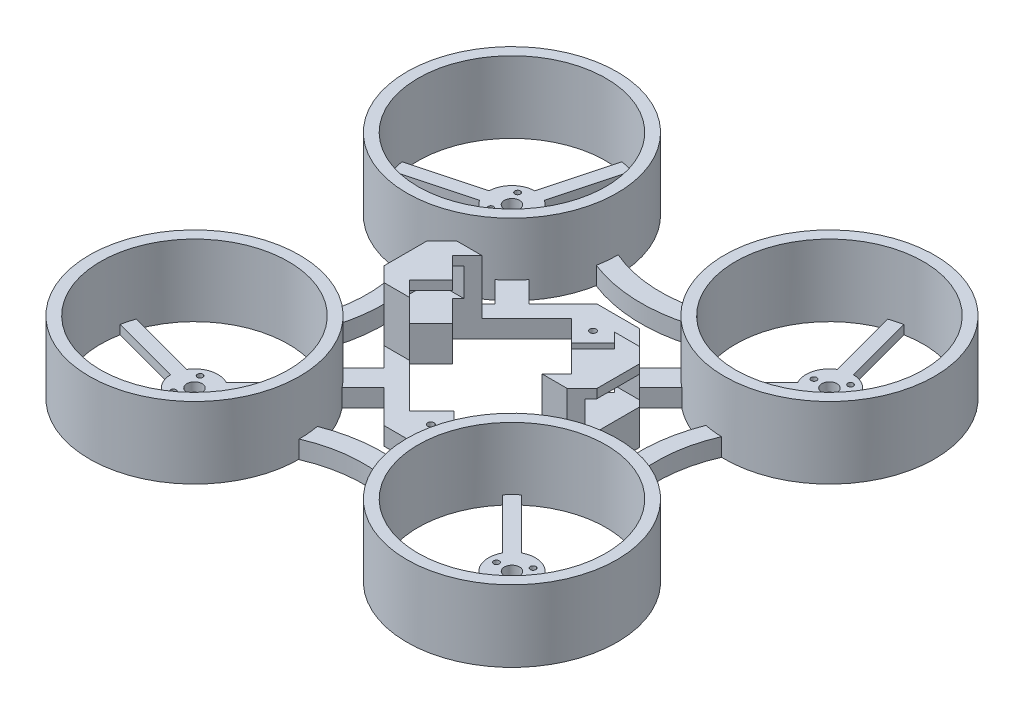
SolidWorks part; units mm, degrees
ref_plane "Front Plane" through (0, 0, 0) normal (0, 0, 1) x (1, 0, 0)
ref_plane "Top Plane" through (0, 0, 0) normal (0, 1, 0) x (1, 0, 0)
ref_plane "Right Plane" through (0, 0, 0) normal (1, 0, 0) x (0, 0, -1)
sketch "Sketch2" plane through (0, 0, 0) normal (0, 1, 0) x (1, 0, 0)
  line L0 (-4.78, 18.125) -> (0, 13.345)
  line L6 (0, 13.345) -> (4.78, 18.125)
  line L11 (-18.1231, 4.7819) -> (-13.3431, 0.0019)
  line L12 (-13.3431, 0.0019) -> (-18.1231, -4.7782)
  line L13 (18.1231, 4.7819) -> (13.3431, 0.0019)
  line L14 (13.3431, 0.0019) -> (18.1231, -4.7782)
  line L15 (4.78, 18.125) -> (18.1231, 4.7819)
  line L17 (4.9922, -17.9092) -> (0, -12.917)
  line L18 (0, -12.917) -> (-4.9922, -17.9092)
  line L23 (18.1231, -4.7782) -> (4.9922, -17.9092)
  line L24 (-4.9922, -17.9092) -> (-18.1231, -4.7782)
  line L25 (-18.1231, 4.7819) -> (-4.78, 18.125)
  line L27 (-55, 0) -> (55, 0) construction
  line L33 (0, -55) -> (0, 55) construction
  line L40 (31.5229, -56.1137) -> (35.6423, -40.74)
  line L41 (28.6252, -55.3372) -> (32.7445, -39.9635)
  line L42 (55.3398, -28.6226) -> (39.9661, -32.742)
  line L43 (55.3398, 28.6226) -> (39.9661, 32.742)
  line L44 (28.6252, 55.3372) -> (32.7445, 39.9635)
  line L45 (56.1162, 31.5204) -> (40.7425, 35.6397)
  line L46 (31.5229, 56.1137) -> (35.6423, 40.74)
  line L47 (56.1162, -31.5204) -> (40.7425, -35.6397)
  line L48 (-28.6252, -55.3372) -> (-32.7445, -39.9635)
  line L49 (-31.5229, -56.1137) -> (-35.6423, -40.74)
  line L50 (-56.1162, -31.5204) -> (-40.7425, -35.6397)
  line L51 (-55.3398, -28.6226) -> (-39.9661, -32.742)
  line L52 (-31.5229, 56.1137) -> (-35.6423, 40.74)
  line L53 (-28.6252, 55.3372) -> (-32.7445, 39.9635)
  line L54 (-55.3398, 28.6226) -> (-39.9661, 32.742)
  line L55 (-56.1162, 31.5204) -> (-40.7425, 35.6397)
  line L56 (-30.8775, 32.9969) -> (-19.6231, 21.7425)
  line L57 (-32.9965, 30.8765) -> (-21.7426, 19.6226)
  line L59 (23.7763, 4.7819) -> (23.7763, -4.7819)
  line L60 (-16.1636, 12.3946) -> (-20.8687, 17.0996)
  line L61 (30.8775, 32.9969) -> (19.6231, 21.7425)
  line L62 (32.9965, 30.8765) -> (21.7426, 19.6226)
  line L63 (-12.3927, 16.1655) -> (-17.0982, 20.871)
  line L65 (12.3927, 16.1655) -> (17.0982, 20.871)
  line L66 (16.1636, 12.3946) -> (20.8687, 17.0996)
  line L70 (32.9965, -30.8765) -> (21.7426, -19.6226)
  line L71 (30.8775, -32.9969) -> (19.6231, -21.7425)
  line L72 (-30.8775, -32.9969) -> (-19.6231, -21.7425)
  line L73 (-32.9965, -30.8765) -> (-21.7426, -19.6226)
  line L75 (-12.3927, -16.1655) -> (-17.0982, -20.871)
  line L76 (-16.1636, -12.3946) -> (-20.8687, -17.0996)
  line L85 (4.9922, -23.566) -> (12.3927, -16.1655)
  line L86 (12.3927, -16.1655) -> (17.0982, -20.871)
  line L87 (16.1636, -12.3946) -> (20.8687, -17.0996)
  line L90 (-23.7763, 4.7819) -> (-23.7763, -4.7819)
  line L91 (-23.7763, 4.7819) -> (-16.1636, 12.3946)
  line L92 (4.78, 23.7781) -> (12.3927, 16.1655)
  line L93 (23.7763, 4.7819) -> (16.1636, 12.3946)
  line L94 (-4.9922, -23.566) -> (4.9922, -23.566)
  line L96 (4.78, 23.7781) -> (-4.78, 23.7781)
  line L97 (-4.78, 23.7781) -> (-12.3927, 16.1655)
  line L98 (16.1636, -12.3946) -> (23.7763, -4.7819)
  line L99 (-4.9922, -23.566) -> (-12.3927, -16.1655)
  line L100 (-16.1636, -12.3946) -> (-23.7763, -4.7819)
  circle A0 centre (0, 18.125) radius 0.7
  circle A1 centre (18.1231, 0.0019) radius 0.7
  circle A2 centre (0, -18.1213) radius 0.7
  circle A3 centre (-18.1231, 0.0019) radius 0.7
  circle A4 centre (-35.4954, 35.4928) radius 5.2492
  circle A5 centre (-32.0291, 35.4951) radius 0.625
  circle A6 centre (-37.2253, 32.4951) radius 0.625
  circle A7 centre (-37.2253, 38.4951) radius 0.625
  circle A8 centre (-35.4954, 35.4928) radius 1.7
  arc A9 (-30.8775, 32.9969) -> (-32.9965, 30.8765) centre (-35.4954, 35.4928) cw
  circle A10 centre (-37.2253, -38.4951) radius 0.625
  circle A11 centre (-32.0291, -35.4951) radius 0.625
  circle A12 centre (-37.2253, -32.4951) radius 0.625
  circle A13 centre (-35.4954, -35.4928) radius 1.7
  circle A14 centre (-35.4954, -35.4928) radius 5.2492
  arc A15 (-30.8775, -32.9969) -> (-32.9965, -30.8765) centre (-35.4954, -35.4928) ccw
  circle A16 centre (37.2253, 38.4951) radius 0.625
  circle A17 centre (32.0291, 35.4951) radius 0.625
  circle A18 centre (35.4954, 35.4928) radius 1.7
  circle A19 centre (37.2253, 32.4951) radius 0.625
  circle A20 centre (35.4954, 35.4928) radius 5.2492
  circle A21 centre (37.2253, -38.4951) radius 0.625
  circle A22 centre (37.2253, -32.4951) radius 0.625
  circle A23 centre (32.0291, -35.4951) radius 0.625
  circle A24 centre (35.4954, -35.4928) radius 1.7
  circle A25 centre (35.4954, -35.4928) radius 5.2492
  arc A26 (30.8775, 32.9969) -> (32.9965, 30.8765) centre (35.4954, 35.4928) ccw
  arc A27 (30.8775, -32.9969) -> (32.9965, -30.8765) centre (35.4954, -35.4928) cw
  circle A28 centre (35.4954, -35.4928) radius 21
  circle A29 centre (-35.4954, -35.4928) radius 21
  circle A30 centre (35.4954, 35.4928) radius 21
  circle A31 centre (-35.4954, 35.4928) radius 21
  circle A32 centre (35.4954, -35.4928) radius 23.5
  circle A33 centre (-35.4954, -35.4928) radius 23.5
  circle A34 centre (-35.4954, 35.4928) radius 23.5
  circle A35 centre (35.4954, 35.4928) radius 23.5
  arc A36 (55.3398, 28.6226) -> (56.1162, 31.5204) centre (35.4954, 35.4928) ccw
  arc A37 (39.9661, 32.742) -> (40.7425, 35.6397) centre (35.4954, 35.4928) ccw
  arc A38 (32.7445, 39.9635) -> (35.6423, 40.74) centre (35.4954, 35.4928) cw
  arc A39 (28.6252, 55.3372) -> (31.5229, 56.1137) centre (35.4954, 35.4928) cw
  arc A40 (-20.8687, 17.0996) -> (-17.0982, 20.871) centre (-35.4954, 35.4928) ccw
  arc A41 (20.8687, 17.0996) -> (17.0982, 20.871) centre (35.4954, 35.4928) cw
  arc A43 (-20.8687, -17.0996) -> (-17.0982, -20.871) centre (-35.4954, -35.4928) cw
  arc A44 (20.8687, -17.0996) -> (17.0982, -20.871) centre (35.4954, -35.4928) ccw
  arc A45 (30.9176, -12.443) -> (30.9176, 12.443) centre (62.3369, 0) cw
  arc A46 (34.8421, -12.0019) -> (30.9176, -12.443) centre (35.4954, -35.4928) ccw
  arc A47 (34.8421, 12.0019) -> (34.8421, -12.0019) centre (62.3369, 0) ccw
  arc A48 (-30.9176, 12.443) -> (-34.8421, 12.0019) centre (-35.4954, 35.4928) cw
  arc A49 (-34.8421, -12.0019) -> (-30.9176, -12.443) centre (-35.4954, -35.4928) cw
  arc A50 (-34.8421, 12.0019) -> (-34.8421, -12.0019) centre (-62.3369, 0) cw
  arc A51 (-30.9176, -12.443) -> (-30.9176, 12.443) centre (-62.3369, 0) ccw
  arc A52 (11.9679, 35.6936) -> (-11.9275, 35.676) centre (0, 63.203) cw
  arc A53 (11.9679, 35.6936) -> (12.3621, 31.1996) centre (35.4954, 35.4928) ccw
  arc A54 (12.3621, 31.1996) -> (-12.3239, 31.1847) centre (0, 62.8445) cw
  arc A55 (-11.9275, 35.676) -> (-12.3239, 31.1847) centre (-35.4954, 35.4928) cw
  arc A56 (30.9176, 12.443) -> (34.8421, 12.0019) centre (35.4954, 35.4928) ccw
  arc A57 (-11.9275, -35.676) -> (-12.3239, -31.1847) centre (-35.4954, -35.4928) ccw
  arc A58 (11.9679, -35.6936) -> (12.3621, -31.1996) centre (35.4954, -35.4928) cw
  arc A59 (12.3621, -31.1996) -> (-12.3239, -31.1847) centre (0, -62.8445) ccw
  arc A60 (11.9679, -35.6936) -> (-11.9275, -35.676) centre (0, -63.203) ccw
  point P162 (-34.8282, -11.5041)
  point P163 (-34.8282, -11.5021)
  point P164 (-30.7361, 11.9711)
  point P165 (-30.7364, 11.9694)
  dimension "D1" = 3.4
  dimension "D2" = 42
  dimension "D3" = 42
  dimension "D4" = 47
  dimension "D5" = 42
  dimension "D6" = 47
  dimension "D7" = 47
  dimension "D8" = 47
  dimension "D9" = 1.4
  dimension "D11" = 1.4
ref_plane "Plane2" through (0, 13, 0) normal (0, 1, 0) x (1, 0, 0)
extrude "Boss-Extrude4" add sketch "Sketch2<15>" along normal blind 2 separate body contours L72 A29 L73 A14 | L51 A29 L50 A14 | L49 A29 L48 A14 | A14 A12 A10 A11 A13 | L41 A28 L40 A25 | L70 A28 L71 A25 | A25 A21 A22 A23 A24 | L47 A28 L42 A25 | L57 A31 L56 A4 | L55 A31 L54 A4 | A4 A8 A7 A6 A5 | L53 A31 L52 A4 | L61 A30 L62 A20 | A20 A18 A16 A17 A19 | L46 A30 L44 A20 | L43 A30 L45 A20 region at (32.1102, 0, 48.1265) region at (34.1752, 0, 40.4197) region at (48.1291, 0, 32.1076) region at (26.2457, 0, 26.2454) region at (48.1291, 0, -32.1076) region at (36.8142, 0, -30.5655) region at (26.2457, 0, -26.2454) region at (32.1102, 0, -48.1265) region at (-32.1102, 0, 48.1265) region at (-34.1752, 0, 40.4197) region at (-48.1291, 0, 32.1076) region at (-26.2457, 0, 26.2454) region at (-32.1102, 0, -48.1265) region at (-34.1752, 0, -40.4197) region at (-48.1291, 0, -32.1076) region at (-26.2457, 0, -26.2454)
sketch "Sketch2<15>" plane through (0, 0, 0) normal (0, 1, 0) x (1, 0, 0) same geometry as "Sketch2"
extrude "Boss-Extrude5" add sketch "Sketch2" along normal blind 16 contours A33 A29 | A32 A28 | A34 A31 | A35 A30 region at (19.3462, 0, -19.348) region at (25.8944, 0, 14.7739) region at (-19.3462, 0, -19.348) region at (-13.9353, 0, 27.9685)
extrude "Boss-Extrude8" add sketch "Sketch2<21>" along normal blind 4 contours A47 A35 A45 A32 | A35 L65 L92 L96 L97 L63 A34 L60 L91 L90 L100 L76 A33 L75 L99 L94 L85 L86 A32 L87 L98 L59 L93 L66 L11 L25 L0 L6 L15 L13 L14 L23 L17 L18 L24 L12 A0 A1 A2 A3 | A33 A51 A34 A50 | A54 A35 A52 A34 | A60 A57 A59 A58 region at (23.1053, 0, 0) region at (31.2389, 0, 0) region at (-31.2389, 0, 0) region at (0.0205, 0, -31.8188)
sketch "Sketch2<21>" plane through (0, 0, 0) normal (0, 1, 0) x (1, 0, 0) same geometry as "Sketch2"
sketch "Sketch20" plane through (0, 4, 0) normal (0, 1, 0) x (1, 0, 0)
  line L3 (-23.7763, 4.7819) -> (-16.1636, 12.3946) construction
  line L4 (-20.4582, 8.1) -> (-14.805, 8.1)
  line L5 (-18.1231, 4.7819) -> (-4.78, 18.125) construction
  line L6 (-14.805, 8.1) -> (-18.1231, 4.7819)
  line L7 (-18.1231, 4.7819) -> (-13.3431, 0.0019)
  line L8 (-13.3431, 0.0019) -> (-18.1231, -4.7782)
  line L10 (-16.1636, -12.3946) -> (-23.7763, -4.7819) construction
  line L11 (-20.4582, -8.1) -> (-14.8013, -8.1)
  line L12 (-4.9922, -17.9092) -> (-18.1231, -4.7782) construction
  line L13 (-14.8013, -8.1) -> (-18.1231, -4.7782)
  line L14 (-23.7763, 4.7819) -> (-20.4582, 8.1)
  line L15 (-20.4582, -8.1) -> (-23.7763, -4.7819)
  line L16 (-23.7763, -4.7819) -> (-23.7763, 4.7819)
  line L17 (0, -55) -> (0, 55) construction
  line L18 (20.4582, -8.1) -> (14.8013, -8.1)
  line L19 (14.8013, -8.1) -> (18.1231, -4.7782)
  line L20 (13.3431, 0.0019) -> (18.1231, -4.7782)
  line L21 (18.1231, 4.7819) -> (13.3431, 0.0019)
  line L22 (14.805, 8.1) -> (18.1231, 4.7819)
  line L23 (20.4582, 8.1) -> (14.805, 8.1)
  line L24 (23.7763, 4.7819) -> (20.4582, 8.1)
  line L25 (23.7763, -4.7819) -> (23.7763, 4.7819)
  line L26 (20.4582, -8.1) -> (23.7763, -4.7819)
extrude "Boss-Extrude10" add sketch "Sketch20" along normal blind 12.2
sketch "Sketch19" plane through (0, 0, 0) normal (1, 0, 0) x (0, 0, -1)
  line L2 (6.1019, 14.2) -> (-6.0981, 14.2)
  line L3 (-6.0981, 14.2) -> (-6.0981, 7.85)
  line L4 (-6.0981, 7.85) -> (6.1019, 7.85)
  line L5 (6.1019, 7.85) -> (6.1019, 14.2)
  point P8 (0.0019, 14.2)
  dimension "D3" = 6.35
extrude "Cut-Extrude2" cut sketch "Sketch19" against normal blind 25.2 and the other way blind 25.2
